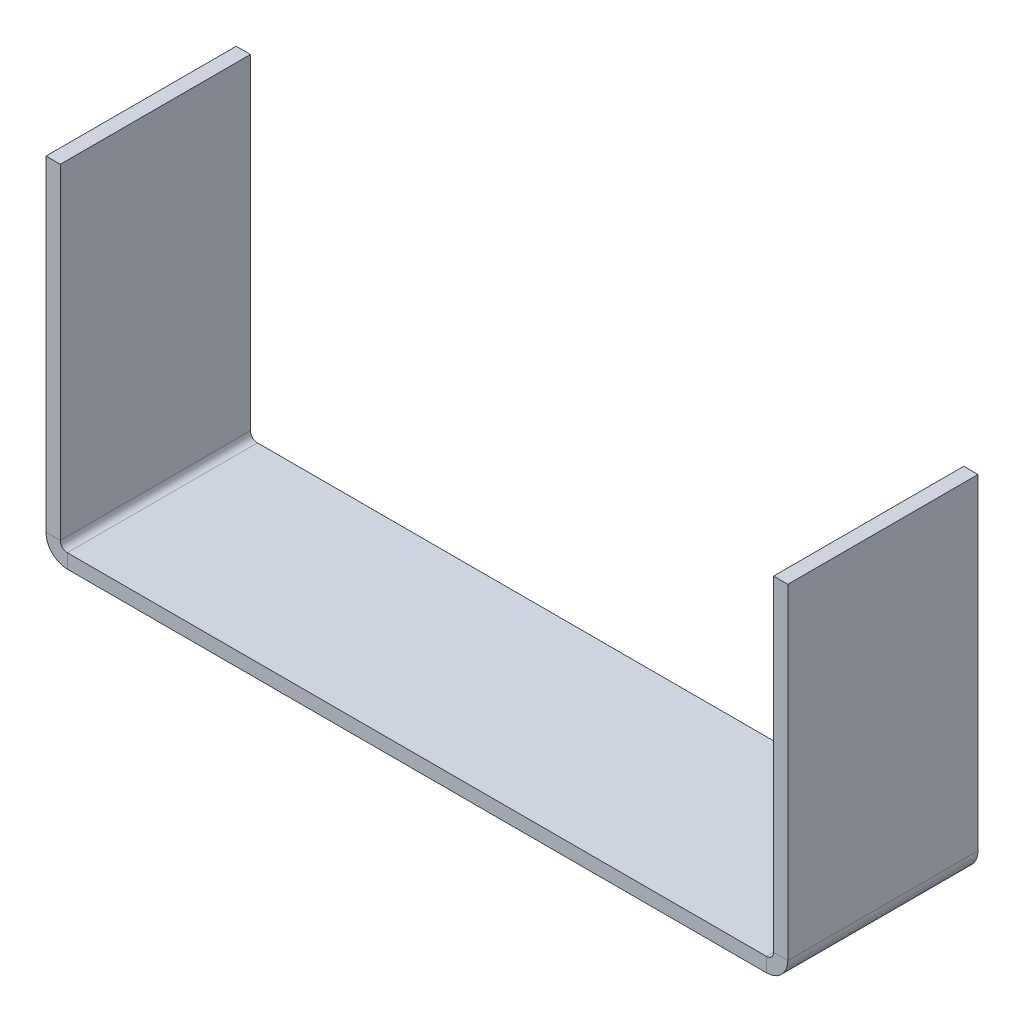
SolidWorks part; units mm, degrees
note: The reader was unsure of these and kept them because the rebuilt part matched: flange length of "Ребро-кромка1", "Ребро-кромка2".
ref_plane "Спереди" through (0, 0, 0) normal (0, 0, 1) x (1, 0, 0)
ref_plane "Сверху" through (0, 0, 0) normal (0, 1, 0) x (1, 0, 0)
ref_plane "Справа" through (0, 0, 0) normal (1, 0, 0) x (0, 0, -1)
sketch "Эскиз1" plane through (0, 0, 0) normal (0, 1, 0) x (1, 0, 0)
  line L1 (0, 0) -> (78, 0)
  line L2 (0, 0) -> (0, 20)
  line L3 (0, 20) -> (78, 20)
  line L4 (78, 0) -> (78, 20)
base flange "Базовая кромка1" sketch "Эскиз1" thickness 1.5 reverse thickness direction no parameters "D1"=0.7366
edge flange "Ребро-кромка1" sketch "Эскиз8" flange angle 90 flange length 36.5 flange position material inside bend radius 0.7366 thickness 1.5 relief rectangular parameters "D6"=10
sketch "Эскиз8" plane through (0, 0, 0) normal (-1, 0, 0) x (0, 0, 1)
  line L0 (-20, 0) -> (0, 0) construction
  line L1 (-20, 0) -> (0, 0)
  line L2 (-20, 0) -> (-20, 35)
  line L3 (-20, 35) -> (0, 35)
  line L4 (0, 35) -> (0, 0)
bend "EdgeBend1" bend radius 0.7366 bend angle 90 parameters "D5"=1
edge flange "Ребро-кромка2" sketch "Эскиз11" flange angle 90 flange length 36.5 flange position material inside bend radius 0.7366 thickness 1.5 relief rectangular parameters "D6"=10
sketch "Эскиз11" plane through (78, 0, 0) normal (1, 0, 0) x (0, 0, -1)
  line L2 (0, 0) -> (0, 35)
  line L3 (0, 35) -> (20, 35)
  line L4 (20, 35) -> (20, 0)
  line L7 (0, 0) -> (20, 0) construction
  line L8 (0, 0) -> (20, 0)
bend "EdgeBend2" bend radius 0.7366 bend angle 90 parameters "D5"=2
sketch "Сгиб-Линии1" [suppressed] plane through (0, 0, 0) normal (0, 1, 0) x (1, 0, 0)
sketch "Граничная рамка1" [suppressed] plane through (0, 0, 0) normal (0, 1, 0) x (1, 0, 0)
sheet metal parameters "Листовой металл1" thickness 1.5 parameters "D1"=0.7366
flat pattern "Развертка1" [suppressed]
sketch "Сгиб-Линии2" plane through (0, 0, 0) normal (0, 1, 0) x (1, 0, 0)
sketch3d "Граничная рамка2" [suppressed]
  line L0 (-200, 20, 0) -> (0, 20, 0) construction
  line L1 (-200, 0, 0) -> (0, 0, 0) construction
  line L2 (-200, 20, 0) -> (-200, 0, 0) construction
  line L3 (0, 20, 0) -> (0, 0, 0) construction
sheet metal parameters "Листовой металл2" thickness 1.5 parameters "D1"=0.7366
flat pattern "Развертка1"
sketch "Сгиб-Линии2" plane through (0, 0, 0) normal (0, 1, 0) x (1, 0, 0)
  line L0 (1.069, 20) -> (1.069, 0) construction
  line L1 (1.069, 20) -> (1.069, 0) construction
sketch3d "Граничная рамка2" [suppressed]
  line L0 (200, 20, 0) -> (-30.5985, 20, 0) construction
  line L1 (200, 0, 0) -> (-30.5985, 0, 0) construction
  line L2 (200, 20, 0) -> (200, 0, 0) construction
  line L3 (-30.5985, 20, 0) -> (-30.5985, 0, 0) construction
bend of the flat pattern "Плоское состояние-<EdgeBend1>1"
sheet metal parameters "Листовой металл3" thickness 1.5 parameters "D1"=0.7366
flat pattern "Развертка1"
sketch "Сгиб-Линии2" plane through (0, 0, 0) normal (0, 1, 0) x (1, 0, 0)
  line L0 (1.069, 20) -> (1.069, 0) construction
  line L1 (1.069, 20) -> (1.069, 0) construction
  line L2 (82.931, 0) -> (82.931, 20) construction
  line L3 (82.931, 0) -> (82.931, 20) construction
sketch3d "Граничная рамка2" [suppressed]
  line L0 (118.3619, 20, 0) -> (-34.3619, 20, 0) construction
  line L1 (118.3619, 0, 0) -> (-34.3619, 0, 0) construction
  line L2 (118.3619, 20, 0) -> (118.3619, 0, 0) construction
  line L3 (-34.3619, 20, 0) -> (-34.3619, 0, 0) construction
bend of the flat pattern "Плоское состояние-<EdgeBend1>1"
bend of the flat pattern "Плоское состояние-<EdgeBend2>1"
